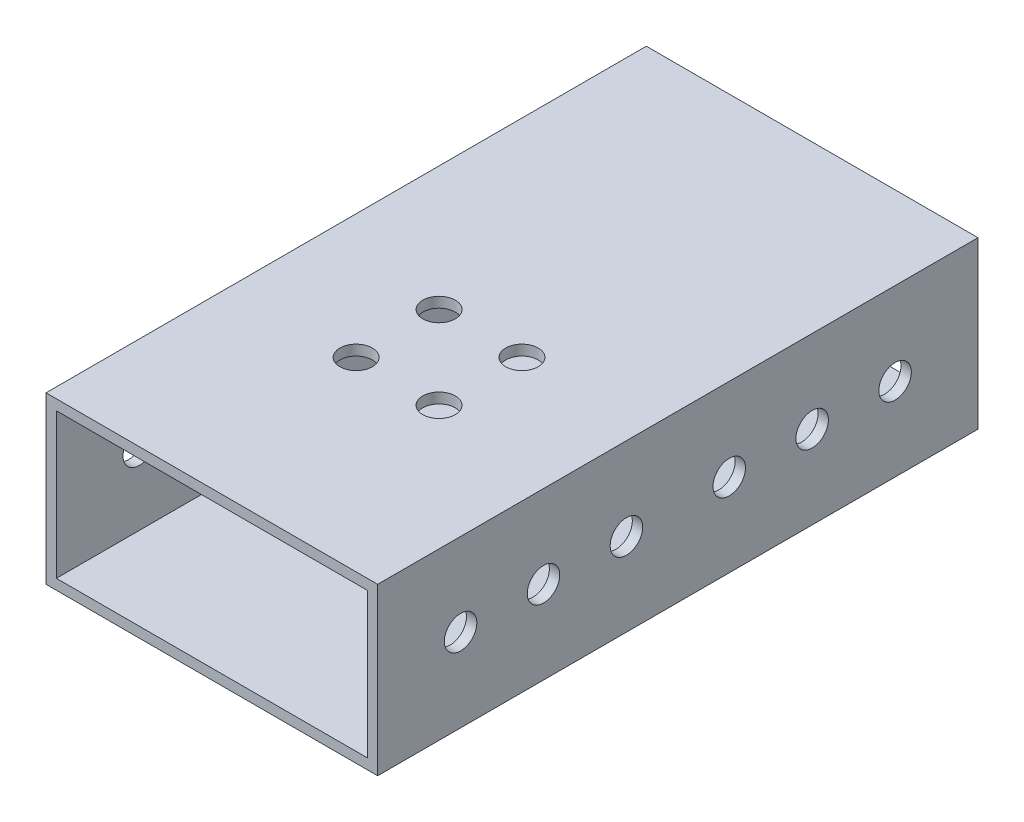
SolidWorks part; units mm, degrees
material "6061-T6 (SS)"
ref_plane "Front Plane" through (0, 0, 0) normal (0, 0, 1) x (1, 0, 0)
ref_plane "Top Plane" through (0, 0, 0) normal (0, 1, 0) x (1, 0, 0)
ref_plane "Right Plane" through (0, 0, 0) normal (1, 0, 0) x (0, 0, -1)
sketch "Sketch1" plane through (0, 0, 0) normal (0, 0, 1) x (1, 0, 0)
  line L1 (-25.4, -12.7) -> (25.4, -12.7)
  line L2 (-25.4, -12.7) -> (-25.4, 12.7)
  line L3 (-25.4, 12.7) -> (25.4, 12.7)
  line L4 (25.4, -12.7) -> (25.4, 12.7)
  line L5 (-25.4, -12.7) -> (25.4, 12.7) construction
  line L6 (-25.4, 12.7) -> (25.4, -12.7) construction
  line L7 (-23.8125, -11.1125) -> (23.8125, -11.1125)
  line L8 (-23.8125, -11.1125) -> (-23.8125, 11.1125)
  line L9 (-23.8125, 11.1125) -> (23.8125, 11.1125)
  line L10 (23.8125, -11.1125) -> (23.8125, 11.1125)
  line L11 (-23.8125, -11.1125) -> (23.8125, 11.1125) construction
  line L12 (-23.8125, 11.1125) -> (23.8125, -11.1125) construction
  point P0 (0, 0)
  point P6 (0, 0)
  dimension "D1" = 50.8
  dimension "D2" = 25.4
  dimension "D3" = 1.5875
  dimension "D4" = 1.5875
extrude "Boss-Extrude1" add sketch "Sketch1" along normal mid plane 91.948
sketch "Sketch2" plane through (0, 12.7, 0) normal (0, 1, 0) x (1, 0, 0)
  line L0 (-6.35, -4.826) -> (6.35, -4.826) construction
  line L2 (25.4, 45.974) -> (-25.4, 45.974) construction
  circle A0 centre (-6.35, -4.826) radius 2.4892
  circle A1 centre (6.35, -4.826) radius 2.4892
  circle A2 centre (-6.35, -17.526) radius 2.4892
  circle A3 centre (6.35, -17.526) radius 2.4892
  point P8 (0, -4.826)
  dimension "D1" = 4.9784
  dimension "D2" = 12.7
  dimension "D3" = 12.7
  dimension "D4" = 50.8
extrude "Cut-Extrude1" cut sketch "Sketch2" against normal through all
sketch "Sketch3" plane through (25.4, 0, 0) normal (1, 0, 0) x (0, 0, -1)
  line L0 (45.974, 12.7) -> (45.974, -12.7) construction
  line L1 (0, 12.7) -> (0, -12.7) construction
  line L2 (-45.974, 12.7) -> (45.974, 12.7) construction
  line L3 (-45.974, -12.7) -> (45.974, -12.7) construction
  circle A0 centre (33.274, 0) radius 2.4892
  circle A1 centre (20.574, 0) radius 2.4892
  circle A2 centre (7.874, 0) radius 2.4892
  circle A3 centre (-33.274, 0) radius 2.4892
  circle A4 centre (-20.574, 0) radius 2.4892
  circle A5 centre (-7.874, 0) radius 2.4892
  point P9 (45.974, 0)
  dimension "D1" = 4.9784
  dimension "D2" = 12.7
  dimension "D3" = 12.7
  dimension "D4" = 12.7
extrude "Cut-Extrude2" cut sketch "Sketch3" against normal through all
